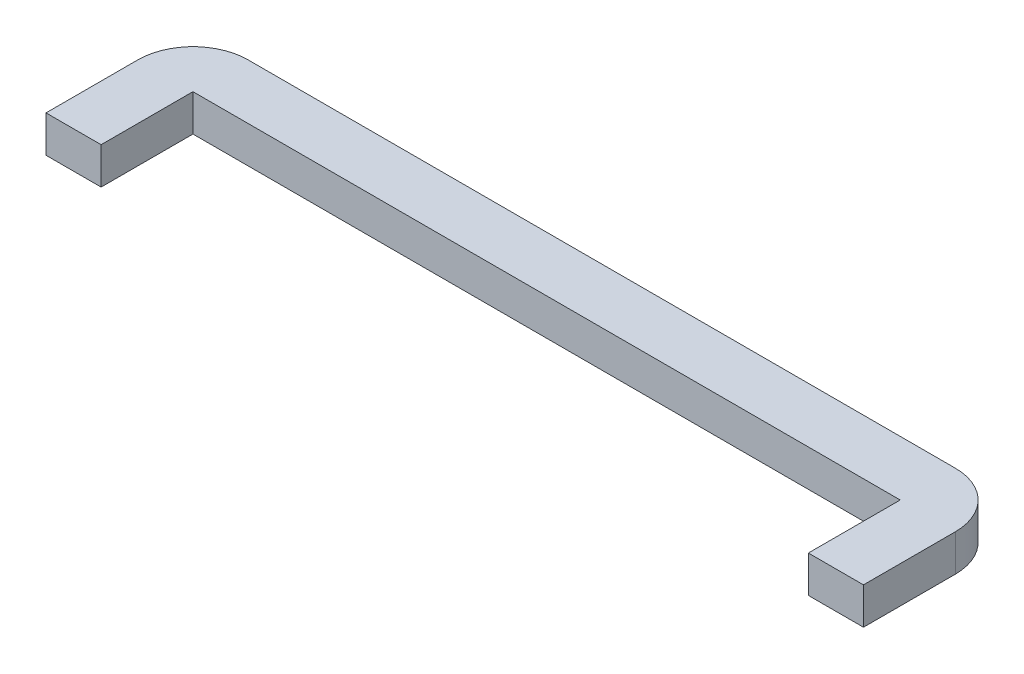
SolidWorks part; units mm, degrees
ref_plane "Front Plane" through (0, 0, 0) normal (0, 0, 1) x (1, 0, 0)
ref_plane "Top Plane" through (0, 0, 0) normal (0, 1, 0) x (1, 0, 0)
ref_plane "Right Plane" through (0, 0, 0) normal (1, 0, 0) x (0, 0, -1)
sketch "Sketch1" plane through (0, 0, 0) normal (0, 1, 0) x (1, 0, 0)
  line L1 (-22.25, -1.5) -> (22.25, -1.5)
  line L2 (-22.25, -1.5) -> (-22.25, 1.5)
  line L3 (-22.25, 1.5) -> (22.25, 1.5)
  line L4 (22.25, -1.5) -> (22.25, 1.5)
  line L5 (-22.25, -1.5) -> (22.25, 1.5) construction
  line L6 (-22.25, 1.5) -> (22.25, -1.5) construction
  line L7 (-22.25, -1.5) -> (-19.25, -1.5)
  line L8 (-22.25, -1.5) -> (-22.25, -6.5)
  line L9 (-22.25, -6.5) -> (-19.25, -6.5)
  line L10 (-19.25, -1.5) -> (-19.25, -6.5)
  line L11 (22.25, -1.5) -> (19.25, -1.5)
  line L12 (22.25, -1.5) -> (22.25, -6.5)
  line L13 (22.25, -6.5) -> (19.25, -6.5)
  line L14 (19.25, -1.5) -> (19.25, -6.5)
  point P0 (0, 0)
  dimension "D1" = 3
  dimension "D2" = 38.5
  dimension "D3" = 3
  dimension "D4" = 5
extrude "Boss-Extrude1" add sketch "Sketch1" along normal mid plane 2 contours L1 L4 L3 L2 | L10 L1 L8 L9 | L1 L14 L13 L12 region at (0, 0, 0) region at (-20.75, 0, 4) region at (20.75, 0, 4)
fillet "Fillet1" radius 3 2 edges at (-22.25, 0, -1.5) (22.25, 0, -1.5)
